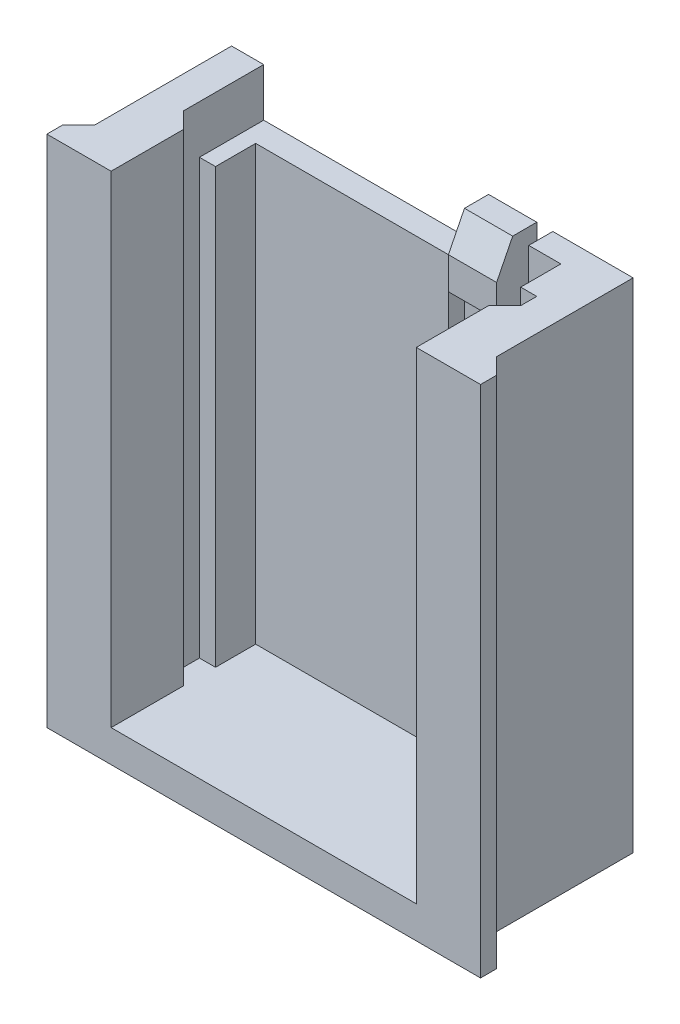
SolidWorks part; units mm, degrees
ref_plane "Front Plane" through (0, 0, 0) normal (0, 0, 1) x (1, 0, 0)
ref_plane "Top Plane" through (0, 0, 0) normal (0, 1, 0) x (1, 0, 0)
ref_plane "Right Plane" through (0, 0, 0) normal (1, 0, 0) x (0, 0, -1)
sketch "Sketch1" plane through (0, 0, 0) normal (0, 1, 0) x (1, 0, 0)
  line L1 (-12.5, -5.25) -> (12.5, -5.25)
  line L2 (-12.5, -5.25) -> (-12.5, 5.25)
  line L3 (-12.5, 5.25) -> (12.5, 5.25)
  line L4 (12.5, -5.25) -> (12.5, 5.25)
  line L5 (-12.5, -5.25) -> (12.5, 5.25) construction
  line L6 (-12.5, 5.25) -> (12.5, -5.25) construction
  point P0 (0, 0)
  dimension "10" = 10.5
  dimension "D2" = 25
extrude "Boss-Extrude1" add sketch "Sketch1" along normal blind 31
sketch "Sketch3" plane through (0, 0, -5.25) normal (0, 0, -1) x (-1, 0, 0)
  line L0 (-17.5, 27) -> (17.5, 27) construction
  line L1 (-17.5, 31) -> (17.5, 31)
  line L2 (-17.5, 23) -> (17.5, 23)
  line L3 (-12.5, 31) -> (12.5, 31) construction
  arc A0 (-17.5, 31) -> (-17.5, 23) centre (-17.5, 27) ccw
  arc A1 (17.5, 23) -> (17.5, 31) centre (17.5, 27) ccw
  point P2 (0, 27)
  dimension "D1" = 8
  dimension "D2" = 35
extrude "Boss-Extrude2" [suppressed] add sketch "Sketch3" against normal up to surface (10.5 mm away)
sketch "Sketch2" plane through (0, 31, 0) normal (0, 1, 0) x (1, 0, 0)
  line L0 (-9.5, 3.75) -> (9.5, 3.75)
  line L1 (-9.5, 3.75) -> (-9.5, 1.25)
  line L2 (-9.5, 1.25) -> (-10.5, 1.25)
  line L3 (-10.5, 1.25) -> (-10.5, -0.75)
  line L4 (-10.5, -0.75) -> (-9.5, -0.75)
  line L5 (-9.5, -0.75) -> (-9.5, -5.25)
  line L6 (-9.5, -5.25) -> (9.5, -5.25)
  line L7 (0, 3.5912) -> (0, -3.9122) construction
  line L8 (9.5, -0.75) -> (9.5, -5.25)
  line L9 (10.5, -0.75) -> (9.5, -0.75)
  line L10 (10.5, 1.25) -> (10.5, -0.75)
  line L11 (9.5, 1.25) -> (10.5, 1.25)
  line L12 (9.5, 3.75) -> (9.5, 1.25)
  line L14 (-12.5, -5.25) -> (12.5, -5.25) construction
  point P12 (0, -5.25)
  point P17 (0, 3.75)
  dimension "D1" = 21
  dimension "D2" = 2
  dimension "D3" = 2.5
  dimension "D4" = 4.5
  dimension "D5" = 19
  dimension "D6" = 19
extrude "Cut-Extrude1" cut sketch "Sketch2" against normal offset from surface (30 mm away) 1 up to face at (0, 0, 0)
sketch "Sketch5" [suppressed] plane through (0, 0, -5.25) normal (0, 0, -1) x (-1, 0, 0)
  circle A0 centre (-17.5, 26) radius 1.75
  circle A1 centre (17.5, 26) radius 1.75
  arc A2 (-17.5, 30) -> (-17.5, 22) centre (-17.5, 26) ccw construction
  dimension "D1" = 3.5
  dimension "D2" = 3.5
extrude "Cut-Extrude2" [suppressed] cut sketch "Sketch5" against normal through all
sketch "Sketch6" plane through (0, 31, 0) normal (0, 1, 0) x (1, 0, 0)
  line L1 (9.5, 3.75) -> (10.5, 3.75)
  line L2 (9.5, 3.75) -> (9.5, 1.25)
  line L3 (9.5, 1.25) -> (10.5, 1.25)
  line L4 (10.5, 3.75) -> (10.5, 1.25)
extrude "Cut-Extrude3" [suppressed] cut sketch "Sketch6" against normal blind 7.5
sketch "Sketch7" [suppressed] plane through (0, 0, -3.5) normal (0, 0, 1) x (1, 0, 0)
  line L0 (10.5, 27) -> (9.5, 27)
  line L1 (10.5, 27) -> (-9.5, 27) construction
  line L2 (9.5, 27) -> (8.5103, 20.1429)
  line L3 (9.5, 1) -> (9.5, 19.5) construction
  line L4 (8.5103, 20.1429) -> (9.5, 20)
  line L5 (9.5, 20) -> (10.2217, 25)
  line L6 (10.2217, 25) -> (10.5, 25)
  line L7 (10.5, 19.5) -> (10.5, 27) construction
  line L8 (10.5, 25) -> (10.5, 27)
  dimension "D1" = 1
  dimension "D2" = 2
  dimension "D3" = 1
  dimension "D4" = 0.5
extrude "Boss-Extrude3" [suppressed] add sketch "Sketch7" along normal up to surface (4.75 mm away) from offset 0.25
sketch "Sketch8" plane through (0, 0, -3.75) normal (0, 0, 1) x (1, 0, 0)
  line L1 (6.5, 29) -> (3.5, 29)
  line L2 (6.5, 29) -> (6.5, 27)
  line L3 (6.5, 27) -> (3.5, 27)
  line L4 (3.5, 29) -> (3.5, 27)
  line L5 (6.5, 29) -> (3.5, 27) construction
  line L6 (6.5, 27) -> (3.5, 29) construction
  line L7 (9.5, 31) -> (-9.5, 31) construction
  point P0 (5, 28)
  dimension "D1" = 4
  dimension "D2" = 2
  dimension "D3" = 3
  dimension "D4" = 5
extrude "Boss-Extrude4" add sketch "Sketch8" along normal blind 1
chamfer "Chamfer1" distance 2 distance2 1 1 edges at (5, 29, -3.75) first distance on face at (0, 16, -3.75)
sketch "Sketch9" plane through (0, 0, -3.75) normal (0, 0, 1) x (1, 0, 0)
  line L0 (3.5, 31) -> (3.5, 18)
  line L1 (3.5, 31) -> (6.5, 31)
  line L2 (6.5, 31) -> (6.5, 18)
  dimension "D1" = 13
extrude "Cut-Extrude-Thin1" cut sketch "Sketch9" against normal through all thin thin type one direction reverse wall 1
sketch "Sketch10" plane through (0, 0, -5.25) normal (0, 0, -1) x (-1, 0, 0)
  line L1 (10.5, 31) -> (-2.5, 31)
  line L2 (10.5, 31) -> (10.5, 28)
  line L3 (10.5, 28) -> (-2.5, 28)
  line L4 (-2.5, 31) -> (-2.5, 28)
  dimension "D1" = 13
  dimension "D2" = 3
extrude "Cut-Extrude5" cut sketch "Sketch10" against normal up to next
sketch "Sketch11" plane through (0, 0, 5.25) normal (0, 0, 1) x (1, 0, 0)
  line L0 (12.5, 31) -> (12.5, 0) construction
  line L1 (-12.5, 0) -> (12.5, 0) construction
  line L2 (-12.5, 31) -> (-12.5, 0) construction
  line L3 (12.5, 31) -> (12.5, 0)
  line L4 (-12.5, 0) -> (12.5, 0)
  line L5 (-12.5, 31) -> (-12.5, 0)
extrude "Extrude-Thin1" add sketch "Sketch11" against normal blind 1 thin thin type one direction wall 1
chamfer "Chamfer2" distance 1 angle 45 3 edges at (-12.5, 15.5, 4.25) (0, 0, 4.25) (12.5, 15.5, 4.25)
chamfer "Chamfer3" distance 1 angle 45 2 edges at (-10.5, 16, 0.75) (10.5, 16, 0.75)
